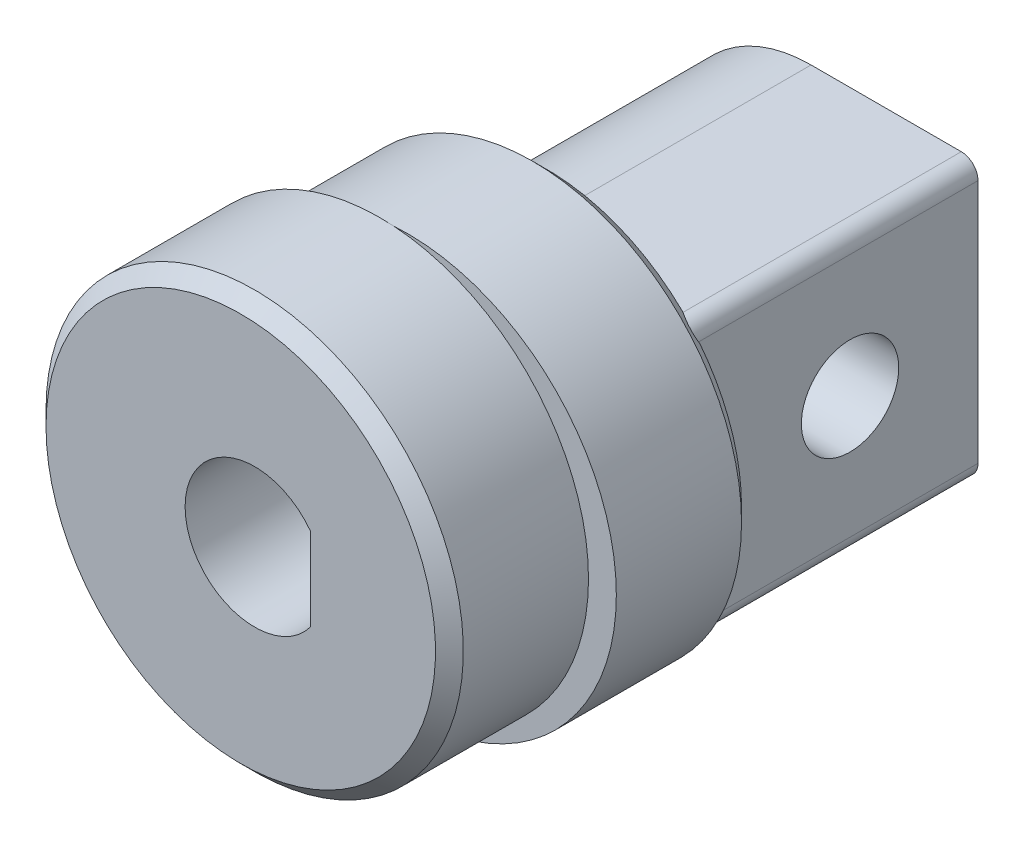
SolidWorks part; units mm, degrees
other "Markup1"
sketch "Sketch20"
ref_plane "Ebene vorne" through (0, 0, 0) normal (0, 0, 1) x (1, 0, 0)
ref_plane "Ebene oben" through (0, 0, 0) normal (0, 1, 0) x (1, 0, 0)
ref_plane "Ebene rechts" through (0, 0, 0) normal (1, 0, 0) x (0, 0, -1)
ref_plane "Plane2" through (0, 0, 0.4) normal (0, 0, 1) x (1, 0, 0)
sketch "Sketch10" plane through (0, 0, 0.4) normal (0, 0, 1) x (1, 0, 0)
  circle A0 centre (0.5, 0) radius 7.5
  dimension "D1" = 15
  dimension "D2" = 0.5
extrude "Boss-Extrude4" add sketch "Sketch10" along normal blind 5
sketch "Sketch11" plane through (0, 0, 0.4) normal (0, 0, -1) x (-1, 0, 0)
  line L0 (-6, -4.4) -> (-6, 4.4)
  line L1 (-5.4, 5) -> (0, 5)
  line L2 (0, -5) -> (-5.4, -5)
  arc A2 (0, 5) -> (0, -5) centre (0, 0) cw
  arc A3 (-6, 4.4) -> (-5.4, 5) centre (-5.4, 4.4) cw
  arc A4 (-5.4, -5) -> (-6, -4.4) centre (-5.4, -4.4) cw
  dimension "D1" = 5
  dimension "D3" = 0.6
  dimension "D2" = 6
extrude "Boss-Extrude5" add sketch "Sketch11" along normal blind 10
sketch "Sketch16" plane through (0, 0, 5.4) normal (0, 0, -1) x (-1, 0, 0)
  circle A0 centre (0.5, 0) radius 7.5
  dimension "D1" = 15
  dimension "D2" = 0.5
extrude "Boss-Extrude6" add sketch "Sketch16" against normal blind 5
sketch "Sketch17" plane through (0, 0, -9.6) normal (0, 0, 1) x (1, 0, 0)
  line L0 (2, -1.5) -> (2, 1.5)
  line L1 (-2.5, 0) -> (-2.5, 1.4955) construction
  arc A0 (2, 1.5) -> (2, -1.5) centre (0, 0) ccw
  dimension "D1" = 2.5
  dimension "D2" = 4.5
extrude "Cut-Extrude2" cut sketch "Sketch17" along normal through all
hole_wizard "Ø3.5 (3.5) Diameter Hole0" positions "Sketch19" profile "Sketch18" hole size "Ø3.5" standard "ANSI Metric"
sketch "Sketch19" plane through (6, 0, 0) normal (1, 0, 0) x (0, 0, -1)
  point P0 (5, 0)
sketch "Sketch18" plane through (6, 0, -5) normal (0, 1, 0) x (0, 0, -1)
  line L0 (0, 0) -> (0, 5.0515)
  line L1 (0, 5.0515) -> (1.75, 4)
  line L2 (1.75, 4) -> (1.75, 0)
  line L5 (1.75, 0) -> (0, 0)
  line L10 (0, 5.0515) -> (-1.75, 4) construction
  line L11 (0, -6.35) -> (0, 107.95) construction
  dimension "Hole Dia." = 3.5
  dimension "Hole Depth" = 4
  dimension "Drill Angle" = 118
chamfer "Chamfer2" distance 0.5 angle 45 2 edges at (-8, 0, 10.4) (8, 0, 0.4)
